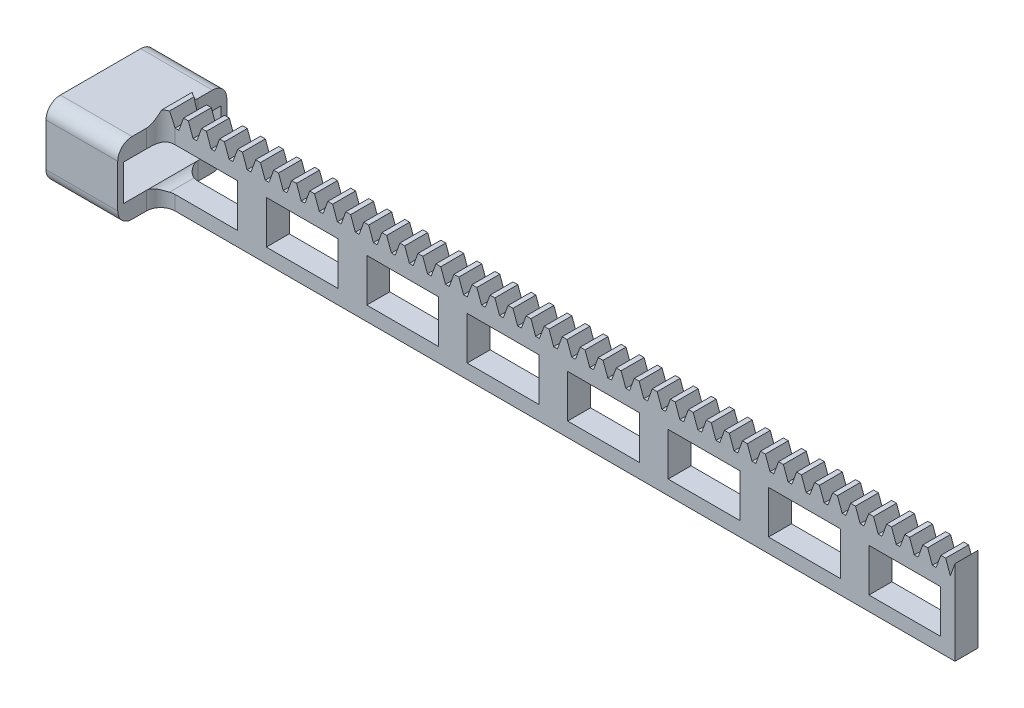
SolidWorks part; units mm, degrees
ref_plane "前视基准面" through (0, 0, 0) normal (0, 0, 1) x (1, 0, 0)
ref_plane "上视基准面" through (0, 0, 0) normal (0, 1, 0) x (1, 0, 0)
ref_plane "右视基准面" through (0, 0, 0) normal (1, 0, 0) x (0, 0, -1)
sketch "草图1" plane through (0, 0, 0) normal (0, 0, 1) x (1, 0, 0)
  line L1 (0, 0) -> (125.6637, 0)
  line L2 (0, 0) -> (0, -10)
  line L3 (0, -10) -> (125.6637, -10)
  line L4 (125.6637, 0) -> (125.6637, -10)
  dimension "D1" = 10
  dimension "L" = 125.6637
extrude "拉伸1" add sketch "草图1" along normal blind 30
sketch "草图2" plane through (0, 0, 30) normal (0, 0, 1) x (1, 0, 0)
  line L0 (0, 0) -> (1.6379, 4.5)
  line L1 (1.6379, 4.5) -> (3.3236, 4.5)
  line L2 (3.3236, 4.5) -> (4.9614, 0)
  line L3 (125.6637, 0) -> (0, 0) construction
  line L4 (0, 0) -> (4.9614, 0)
  line L5 (0.9099, 2.5) -> (4.0515, 2.5) construction
  dimension "D2" = 70
  dimension "alpha" = 110
  dimension "ha" = 2
  dimension "hf" = 2.5
  dimension "S" = 3.1416
extrude "拉伸2" add sketch "草图2" against normal up to surface (30 mm away) up to face at (62.8319, -5, 0)
pattern_linear "阵列(线性)1" count 20 spacing 6.2832 along (1, 0, 0) of "拉伸2"
sketch "草图3" plane through (0, 0, 30) normal (0, 0, 1) x (1, 0, 0)
  line L83 (0, 0) -> (0, -10)
  line L84 (0, -10) -> (125.6637, -10)
  line L85 (125.6637, -10) -> (125.6637, 0)
  line L86 (125.6637, 0) -> (124.342, 0)
  line L87 (124.342, 0) -> (122.7041, 4.5)
  line L88 (122.7041, 4.5) -> (121.0184, 4.5)
  line L89 (121.0184, 4.5) -> (119.3805, 0)
  line L90 (119.3805, 0) -> (118.0588, 0)
  line L91 (118.0588, 0) -> (116.4209, 4.5)
  line L92 (116.4209, 4.5) -> (114.7352, 4.5)
  line L93 (114.7352, 4.5) -> (113.0973, 0)
  line L94 (113.0973, 0) -> (111.7756, 0)
  line L95 (111.7756, 0) -> (110.1377, 4.5)
  line L96 (110.1377, 4.5) -> (108.452, 4.5)
  line L97 (108.452, 4.5) -> (106.8142, 0)
  line L98 (106.8142, 0) -> (105.4924, 0)
  line L99 (105.4924, 0) -> (103.8545, 4.5)
  line L100 (103.8545, 4.5) -> (102.1688, 4.5)
  line L101 (102.1688, 4.5) -> (100.531, 0)
  line L102 (100.531, 0) -> (99.2092, 0)
  line L103 (99.2092, 0) -> (97.5714, 4.5)
  line L104 (97.5714, 4.5) -> (95.8856, 4.5)
  line L105 (95.8856, 4.5) -> (94.2478, 0)
  line L106 (94.2478, 0) -> (92.926, 0)
  line L107 (92.926, 0) -> (91.2882, 4.5)
  line L108 (91.2882, 4.5) -> (89.6025, 4.5)
  line L109 (89.6025, 4.5) -> (87.9646, 0)
  line L110 (87.9646, 0) -> (86.6429, 0)
  line L111 (86.6429, 0) -> (85.005, 4.5)
  line L112 (85.005, 4.5) -> (83.3193, 4.5)
  line L113 (83.3193, 4.5) -> (81.6814, 0)
  line L114 (81.6814, 0) -> (80.3597, 0)
  line L115 (80.3597, 0) -> (78.7218, 4.5)
  line L116 (78.7218, 4.5) -> (77.0361, 4.5)
  line L117 (77.0361, 4.5) -> (75.3982, 0)
  line L118 (75.3982, 0) -> (74.0765, 0)
  line L119 (74.0765, 0) -> (72.4386, 4.5)
  line L120 (72.4386, 4.5) -> (70.7529, 4.5)
  line L121 (70.7529, 4.5) -> (69.115, 0)
  line L122 (69.115, 0) -> (67.7933, 0)
  line L123 (67.7933, 0) -> (66.1554, 4.5)
  line L124 (66.1554, 4.5) -> (64.4697, 4.5)
  line L125 (64.4697, 4.5) -> (62.8319, 0)
  line L126 (62.8319, 0) -> (61.5101, 0)
  line L127 (61.5101, 0) -> (59.8722, 4.5)
  line L128 (59.8722, 4.5) -> (58.1865, 4.5)
  line L129 (58.1865, 4.5) -> (56.5487, 0)
  line L130 (56.5487, 0) -> (55.2269, 0)
  line L131 (55.2269, 0) -> (53.5891, 4.5)
  line L132 (53.5891, 4.5) -> (51.9033, 4.5)
  line L133 (51.9033, 4.5) -> (50.2655, 0)
  line L134 (50.2655, 0) -> (48.9437, 0)
  line L135 (48.9437, 0) -> (47.3059, 4.5)
  line L136 (47.3059, 4.5) -> (45.6202, 4.5)
  line L137 (45.6202, 4.5) -> (43.9823, 0)
  line L138 (43.9823, 0) -> (42.6606, 0)
  line L139 (42.6606, 0) -> (41.0227, 4.5)
  line L140 (41.0227, 4.5) -> (39.337, 4.5)
  line L141 (39.337, 4.5) -> (37.6991, 0)
  line L142 (37.6991, 0) -> (36.3774, 0)
  line L143 (36.3774, 0) -> (34.7395, 4.5)
  line L144 (34.7395, 4.5) -> (33.0538, 4.5)
  line L145 (33.0538, 4.5) -> (31.4159, 0)
  line L146 (31.4159, 0) -> (30.0942, 0)
  line L147 (30.0942, 0) -> (28.4563, 4.5)
  line L148 (28.4563, 4.5) -> (26.7706, 4.5)
  line L149 (26.7706, 4.5) -> (25.1327, 0)
  line L150 (25.1327, 0) -> (23.811, 0)
  line L151 (23.811, 0) -> (22.1731, 4.5)
  line L152 (22.1731, 4.5) -> (20.4874, 4.5)
  line L153 (20.4874, 4.5) -> (18.8496, 0)
  line L154 (18.8496, 0) -> (17.5278, 0)
  line L155 (17.5278, 0) -> (15.8899, 4.5)
  line L156 (15.8899, 4.5) -> (14.2042, 4.5)
  line L157 (14.2042, 4.5) -> (12.5664, 0)
  line L158 (12.5664, 0) -> (11.2446, 0)
  line L159 (11.2446, 0) -> (9.6068, 4.5)
  line L160 (9.6068, 4.5) -> (7.9211, 4.5)
  line L161 (7.9211, 4.5) -> (6.2832, 0)
  line L162 (6.2832, 0) -> (4.9614, 0)
  line L163 (4.9614, 0) -> (3.3236, 4.5)
  line L164 (3.3236, 4.5) -> (1.6379, 4.5)
  line L165 (1.6379, 4.5) -> (0, 0)
  line L166 (0, 0) -> (0, -10)
  line L167 (0, -10) -> (125.6637, -10)
  line L168 (125.6637, -10) -> (125.6637, 0)
  line L169 (125.6637, 0) -> (124.342, 0)
  line L170 (124.342, 0) -> (122.7041, 4.5)
  line L171 (122.7041, 4.5) -> (121.0184, 4.5)
  line L172 (121.0184, 4.5) -> (119.3805, 0)
  line L173 (119.3805, 0) -> (118.0588, 0)
  line L174 (118.0588, 0) -> (116.4209, 4.5)
  line L175 (116.4209, 4.5) -> (114.7352, 4.5)
  line L176 (114.7352, 4.5) -> (113.0973, 0)
  line L177 (113.0973, 0) -> (111.7756, 0)
  line L178 (111.7756, 0) -> (110.1377, 4.5)
  line L179 (110.1377, 4.5) -> (108.452, 4.5)
  line L180 (108.452, 4.5) -> (106.8142, 0)
  line L181 (106.8142, 0) -> (105.4924, 0)
  line L182 (105.4924, 0) -> (103.8545, 4.5)
  line L183 (103.8545, 4.5) -> (102.1688, 4.5)
  line L184 (102.1688, 4.5) -> (100.531, 0)
  line L185 (100.531, 0) -> (99.2092, 0)
  line L186 (99.2092, 0) -> (97.5714, 4.5)
  line L187 (97.5714, 4.5) -> (95.8856, 4.5)
  line L188 (95.8856, 4.5) -> (94.2478, 0)
  line L189 (94.2478, 0) -> (92.926, 0)
  line L190 (92.926, 0) -> (91.2882, 4.5)
  line L191 (91.2882, 4.5) -> (89.6025, 4.5)
  line L192 (89.6025, 4.5) -> (87.9646, 0)
  line L193 (87.9646, 0) -> (86.6429, 0)
  line L194 (86.6429, 0) -> (85.005, 4.5)
  line L195 (85.005, 4.5) -> (83.3193, 4.5)
  line L196 (83.3193, 4.5) -> (81.6814, 0)
  line L197 (81.6814, 0) -> (80.3597, 0)
  line L198 (80.3597, 0) -> (78.7218, 4.5)
  line L199 (78.7218, 4.5) -> (77.0361, 4.5)
  line L200 (77.0361, 4.5) -> (75.3982, 0)
  line L201 (75.3982, 0) -> (74.0765, 0)
  line L202 (74.0765, 0) -> (72.4386, 4.5)
  line L203 (72.4386, 4.5) -> (70.7529, 4.5)
  line L204 (70.7529, 4.5) -> (69.115, 0)
  line L205 (69.115, 0) -> (67.7933, 0)
  line L206 (67.7933, 0) -> (66.1554, 4.5)
  line L207 (66.1554, 4.5) -> (64.4697, 4.5)
  line L208 (64.4697, 4.5) -> (62.8319, 0)
  line L209 (62.8319, 0) -> (61.5101, 0)
  line L210 (61.5101, 0) -> (59.8722, 4.5)
  line L211 (59.8722, 4.5) -> (58.1865, 4.5)
  line L212 (58.1865, 4.5) -> (56.5487, 0)
  line L213 (56.5487, 0) -> (55.2269, 0)
  line L214 (55.2269, 0) -> (53.5891, 4.5)
  line L215 (53.5891, 4.5) -> (51.9033, 4.5)
  line L216 (51.9033, 4.5) -> (50.2655, 0)
  line L217 (50.2655, 0) -> (48.9437, 0)
  line L218 (48.9437, 0) -> (47.3059, 4.5)
  line L219 (47.3059, 4.5) -> (45.6202, 4.5)
  line L220 (45.6202, 4.5) -> (43.9823, 0)
  line L221 (43.9823, 0) -> (42.6606, 0)
  line L222 (42.6606, 0) -> (41.0227, 4.5)
  line L223 (41.0227, 4.5) -> (39.337, 4.5)
  line L224 (39.337, 4.5) -> (37.6991, 0)
  line L225 (37.6991, 0) -> (36.3774, 0)
  line L226 (36.3774, 0) -> (34.7395, 4.5)
  line L227 (34.7395, 4.5) -> (33.0538, 4.5)
  line L228 (33.0538, 4.5) -> (31.4159, 0)
  line L229 (31.4159, 0) -> (30.0942, 0)
  line L230 (30.0942, 0) -> (28.4563, 4.5)
  line L231 (28.4563, 4.5) -> (26.7706, 4.5)
  line L232 (26.7706, 4.5) -> (25.1327, 0)
  line L233 (25.1327, 0) -> (23.811, 0)
  line L234 (23.811, 0) -> (22.1731, 4.5)
  line L235 (22.1731, 4.5) -> (20.4874, 4.5)
  line L236 (20.4874, 4.5) -> (18.8496, 0)
  line L237 (18.8496, 0) -> (17.5278, 0)
  line L238 (17.5278, 0) -> (15.8899, 4.5)
  line L239 (15.8899, 4.5) -> (14.2042, 4.5)
  line L240 (14.2042, 4.5) -> (12.5664, 0)
  line L241 (12.5664, 0) -> (11.2446, 0)
  line L242 (11.2446, 0) -> (9.6068, 4.5)
  line L243 (9.6068, 4.5) -> (7.9211, 4.5)
  line L244 (7.9211, 4.5) -> (6.2832, 0)
  line L245 (6.2832, 0) -> (4.9614, 0)
  line L246 (4.9614, 0) -> (3.3236, 4.5)
  line L247 (3.3236, 4.5) -> (1.6379, 4.5)
  line L248 (1.6379, 4.5) -> (0, 0)
  dimension "D1" = 0
extrude "切除-拉伸1" cut sketch "草图3" against normal blind 22
sketch "草图4" plane through (0, 0, 0) normal (0, 0, -1) x (-1, 0, 0)
  line L0 (-121.8612, 4.5) -> (-121.8612, -10)
  line L1 (-121.0184, 4.5) -> (-122.7041, 4.5) construction
  line L2 (0, -10) -> (-125.6637, -10) construction
  line L3 (-125.6637, 0) -> (-124.342, 0) construction
  line L4 (-125.6637, -10) -> (-125.6637, 0) construction
  line L5 (-122.7041, 4.5) -> (-124.342, 0) construction
  line L6 (-121.8612, -10) -> (-125.6637, -10)
  line L7 (-125.6637, 0) -> (-124.342, 0)
  line L8 (-125.6637, -10) -> (-125.6637, 0)
  line L9 (-121.8612, 4.5) -> (-122.7041, 4.5)
  line L10 (-122.7041, 4.5) -> (-124.342, 0)
extrude "切除-拉伸2" cut sketch "草图4" against normal up to next
mirror "镜向1" about plane through (121.8612, 4.5, 8.001) normal (-1, 0, 0) of bodies 105
sketch "草图5" plane through (0, 0, 0) normal (0, 0, -1) x (-1, 0, 0)
  line L0 (-241.2418, 4.5) -> (-241.2418, -10)
  line L1 (-242.0846, 4.5) -> (-240.3989, 4.5) construction
  line L2 (0, -10) -> (-243.7225, -10) construction
  line L3 (-243.7225, 0) -> (-242.0846, 4.5) construction
  line L4 (-243.7225, 0) -> (-243.7225, -10) construction
  line L5 (-241.2418, -10) -> (-243.7225, -10)
  line L6 (-242.0846, 4.5) -> (-241.2418, 4.5)
  line L7 (-243.7225, 0) -> (-242.0846, 4.5)
  line L8 (-243.7225, 0) -> (-243.7225, -10)
extrude "切除-拉伸3" cut sketch "草图5" against normal up to next
mirror "镜向2" about plane through (241.2418, 4.5, 8.001) normal (-1, 0, 0) of bodies 107
sketch "草图7" plane through (0, 0, 0) normal (0, 0, -1) x (-1, 0, 0)
  line L1 (-275.1384, 4.5785) -> (-482.4835, 4.5785)
  line L2 (-275.1384, 4.5785) -> (-275.1384, -10)
  line L3 (-275.1384, -10) -> (-482.4835, -10)
  line L4 (-482.4835, 4.5785) -> (-482.4835, -10)
  point P6 (-278.098, 4.5)
  point P7 (-275.1974, 4.5785)
extrude "切除-拉伸6" cut sketch "草图7" against normal up to next
mirror "镜向4" about plane through (275.1384, 4.5785, 8.001) normal (-1, 0, 0) of bodies 112
sketch "草图9" plane through (0, 0, 0) normal (0, 0, -1) x (-1, 0, 0)
  line L1 (-276.7763, 5.2464) -> (-555.7489, 5.2464)
  line L2 (-276.7763, 5.2464) -> (-276.7763, -13.7938)
  line L3 (-276.7763, -13.7938) -> (-555.7489, -13.7938)
  line L4 (-555.7489, 5.2464) -> (-555.7489, -13.7938)
extrude "切除-拉伸7" cut sketch "草图9" against normal up to next
sketch "草图10" plane through (0, 0, 0) normal (-1, 0, 0) x (0, 0, 1)
  line L0 (8, 0) -> (8, -10) construction
  line L1 (0, -10) -> (8, -10)
  line L2 (0, -10) -> (0, -25)
  line L3 (0, -25) -> (8, -25)
  line L4 (8, -10) -> (8, -25)
  dimension "D1" = 15
extrude "凸台-拉伸1" add sketch "草图10" along direction (-1, 0, 0) on the side against the normal up to surface (276.7763 mm away) up to face at (276.7763, -2.75, 4)
sketch "草图11" plane through (0, 0, 0) normal (-1, 0, 0) x (0, 0, 1)
  line L0 (-15, 0) -> (23, 0)
  line L1 (-15, 0) -> (-15, -25)
  line L2 (-15, -25) -> (23, -25)
  line L3 (23, 0) -> (23, -25)
  line L4 (4, 0) -> (4, -25) construction
  line L5 (-15, -12.5) -> (-16.4648, -12.5) construction
  line L6 (0, -12.5) -> (2.4226, -12.5)
  line L7 (0, 0) -> (0, -25) construction
  line L8 (0, -25) -> (8, -25) construction
  circle A0 centre (-10, -16) radius 1.25
  circle A1 centre (-10, -9) radius 1.25
  circle A2 centre (18, -9) radius 1.25
  circle A3 centre (18, -16) radius 1.25
  point P3 (4, -25)
  dimension "D3" = 2.5
  dimension "D1" = 28
  dimension "D2" = 7
  dimension "D4" = 5
  dimension "D5" = 9
  dimension "D6" = 5
  dimension "D7" = 9
extrude "凸台-拉伸2" add sketch "草图11" along normal blind 25 contours L0 L3 L2 L1 | A1 | A3 | A2 | A0
sketch "草图12" plane through (0, 0, 0) normal (0, 0, -1) x (-1, 0, 0)
  line L0 (-276.7763, -25) -> (-276.7763, 4.5) construction
  line L1 (-271.7763, -5) -> (-246.7763, -5)
  line L2 (-271.7763, -5) -> (-271.7763, -20)
  line L3 (-271.7763, -20) -> (-246.7763, -20)
  line L4 (-246.7763, -5) -> (-246.7763, -20)
  line L5 (-236.7763, -5) -> (-236.7763, -20)
  line L6 (-236.7763, -5) -> (-211.7763, -5)
  line L7 (-275.1384, 0) -> (-275.1384, -25) construction
  line L8 (-276.7763, -25) -> (0, -25) construction
  line L9 (-275.1384, -12.5) -> (-280.8114, -12.5) construction
  line L10 (-271.7763, -12.5) -> (-263.3686, -12.5) construction
  line L11 (-211.7763, -5) -> (-211.7763, -20)
  line L12 (-236.7763, -20) -> (-211.7763, -20)
  line L13 (-201.7763, -5) -> (-201.7763, -20)
  line L14 (-201.7763, -5) -> (-176.7763, -5)
  line L15 (-176.7763, -5) -> (-176.7763, -20)
  line L16 (-201.7763, -20) -> (-176.7763, -20)
  line L17 (-166.7763, -5) -> (-166.7763, -20)
  line L18 (-166.7763, -5) -> (-141.7763, -5)
  line L19 (-141.7763, -5) -> (-141.7763, -20)
  line L20 (-166.7763, -20) -> (-141.7763, -20)
  line L21 (-131.7763, -5) -> (-131.7763, -20)
  line L22 (-131.7763, -5) -> (-106.7763, -5)
  line L23 (-106.7763, -5) -> (-106.7763, -20)
  line L24 (-131.7763, -20) -> (-106.7763, -20)
  line L25 (-96.7763, -5) -> (-96.7763, -20)
  line L26 (-96.7763, -5) -> (-71.7763, -5)
  line L27 (-71.7763, -5) -> (-71.7763, -20)
  line L28 (-96.7763, -20) -> (-71.7763, -20)
  line L29 (-61.7763, -5) -> (-61.7763, -20)
  line L30 (-61.7763, -5) -> (-36.7763, -5)
  line L31 (-36.7763, -5) -> (-36.7763, -20)
  line L32 (-61.7763, -20) -> (-36.7763, -20)
  line L33 (-26.7763, -5) -> (-26.7763, -20)
  line L34 (-26.7763, -5) -> (-1.7763, -5)
  line L35 (-1.7763, -5) -> (-1.7763, -20)
  line L36 (-26.7763, -20) -> (-1.7763, -20)
  dimension "D1" = 25
  dimension "D2" = 15
  dimension "D3" = 5
  dimension "D4" = 8
extrude "切除-拉伸9" cut sketch "草图12" against normal up to next
sketch "草图13" plane through (0, 0, 0) normal (0, 0, -1) x (-1, 0, 0)
  line L0 (0, 0) -> (0, -25) construction
  line L1 (-1.7763, -5) -> (0, -5)
  line L2 (-1.7763, -5) -> (-1.7763, -20)
  line L3 (-1.7763, -20) -> (0, -20)
  line L4 (0, -5) -> (0, -20)
  line L5 (-26.7763, -20) -> (-1.7763, -20) construction
extrude "切除-拉伸10" cut sketch "草图13" against normal up to next
sketch "草图14" plane through (0, 0, 0) normal (1, 0, 0) x (0, 0, -1)
  line L0 (-18, -9) -> (10, -16) construction
  line L5 (10, -9) -> (-18, -16) construction
  line L7 (-21, -6.25) -> (13, -6.25)
  line L8 (-21, -6.25) -> (-21, -18.75)
  line L9 (-21, -18.75) -> (13, -18.75)
  line L10 (13, -6.25) -> (13, -18.75)
  line L11 (-21, -6.25) -> (13, -18.75) construction
  line L12 (-21, -18.75) -> (13, -6.25) construction
  point P0 (-4, -12.5)
  point P8 (-4, -12.5)
  dimension "D1" = 34
  dimension "D2" = 12.5
extrude "切除-拉伸11" cut sketch "草图14" against normal blind 20
sketch "草图15" plane through (-25, 0, 0) normal (-1, 0, 0) x (0, 0, 1)
  line L0 (-10, -9) -> (18, -16) construction
  line L1 (18, -9) -> (-10, -16) construction
  line L3 (-7.75, -6.25) -> (15.75, -6.25)
  line L4 (-7.75, -6.25) -> (-7.75, -18.75)
  line L5 (-7.75, -18.75) -> (15.75, -18.75)
  line L6 (15.75, -6.25) -> (15.75, -18.75)
  line L7 (-7.75, -6.25) -> (15.75, -18.75) construction
  line L8 (-7.75, -18.75) -> (15.75, -6.25) construction
  point P8 (4, -12.5)
  point P9 (4, -12.5)
  dimension "D1" = 23.5
  dimension "D2" = 12.5
extrude "切除-拉伸12" cut sketch "草图15" against normal up to next
fillet "圆角1" radius 5 4 edges at (-12.5, -25, -15) (-12.5, -25, 23) (-12.5, 0, 23) (-12.5, 0, -15)
fillet "圆角2" radius 5 6 edges at (0, -22.5, 0) (0, -20, 4) (0, -22.5, 8) (0, -2.5, 8) (0, -5, 4) (0, -2.5, 0)
sketch "草图17" plane through (0, 0, 8) normal (0, 0, 1) x (1, 0, 0)
  line L0 (274.3195, 2.25) -> (278.7764, 2.25) construction
equation "\"d\"=\"S@草图2\" * 2"
equation "\"z\"= int(  \"L@草图1\" / (  \"S@草图2\" * 2 ) + 0.5 )"
